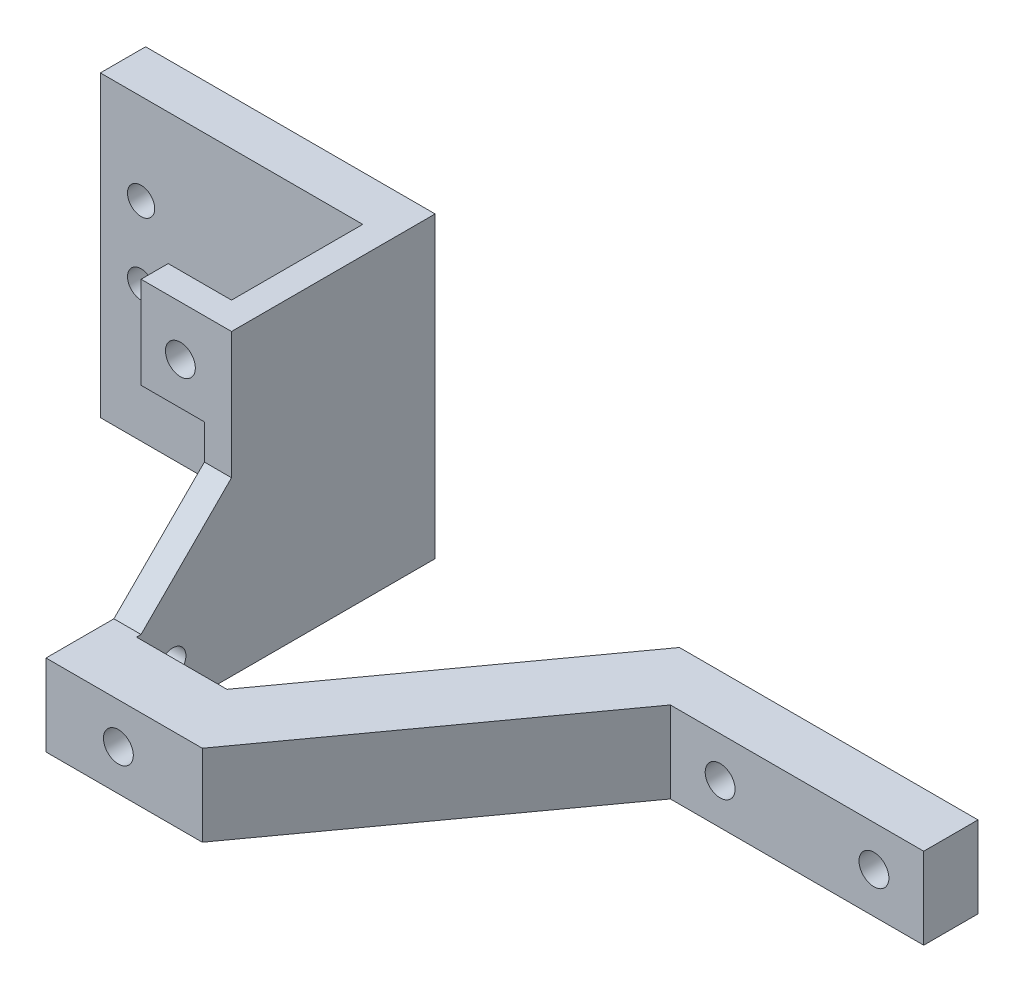
SolidWorks part; units mm, degrees
ref_plane "Płaszczyzna przednia" through (0, 0, 0) normal (0, 0, 1) x (1, 0, 0)
ref_plane "Płaszczyzna górna" through (0, 0, 0) normal (0, 1, 0) x (1, 0, 0)
ref_plane "Płaszczyzna prawa" through (0, 0, 0) normal (1, 0, 0) x (0, 0, -1)
sketch "Szkic1" plane through (0, 0, 0) normal (0, 0, 1) x (1, 0, 0)
  line L0 (0, 0) -> (28, 0)
  line L1 (28, 0) -> (28, 9)
  line L2 (28, 9) -> (0, 9)
  line L3 (0, 9) -> (0, 0)
  line L4 (0, 4.5) -> (28, 4.5) construction
  circle A0 centre (5.5, 4.5) radius 1.65
  circle A1 centre (22.5, 4.5) radius 1.65
  dimension "D3" = 17
  dimension "D1" = 28
  dimension "D2" = 9
  dimension "D4" = 5.5
extrude "Dodanie-wyciągnięcie1" add sketch "Szkic1" along normal blind 6
sketch "Szkic2" plane through (0, 0, 0) normal (0, -1, 0) x (1, 0, 0)
  line L0 (0, 0) -> (-5, 0)
  line L1 (-5, 0) -> (-26, 29.009)
  line L2 (-26, 29.009) -> (-36, 29.009)
  line L3 (-36, 29.009) -> (-36, 36.009)
  line L4 (-36, 36.009) -> (-21.7239, 36.009)
  line L5 (-21.7239, 36.009) -> (0, 6)
  line L6 (0, 6) -> (0, 0)
  dimension "D1" = 21
  dimension "D2" = 7
  dimension "D3" = 5
  dimension "D4" = 10
  dimension "D5" = 14.2761
extrude "Dodanie-wyciągnięcie2" add sketch "Szkic2" against normal up to surface (9 mm away) up to face at (14, 9, 3)
sketch "Szkic3" plane through (0, 0, 0) normal (0, -1, 0) x (1, 0, 0)
  line L0 (-5, 0) -> (28, 0) construction
  line L1 (-36, 36.009) -> (-39, 36.009)
  line L2 (-36, 36.009) -> (-36, -4)
  line L3 (-36, -4) -> (-39, -4)
  line L4 (-39, 36.009) -> (-39, -4)
  dimension "D1" = 3
  dimension "D2" = 4
extrude "Dodanie-wyciągnięcie3" add sketch "Szkic3" against normal up to surface (9 mm away) up to face at (-8.5905, 9, 17.7545)
sketch "Szkic10" plane through (0, 0, 36.009) normal (0, 0, 1) x (1, 0, 0)
  line L0 (-39, 4.5) -> (-21.7239, 4.5) construction
  line L1 (-39, 9) -> (-39, 0) construction
  line L2 (-21.7239, 9) -> (-21.7239, 0) construction
  circle A0 centre (-31, 4.5) radius 1.65
  dimension "D1" = 8
extrude "Wytnij-wyciągnięcie4" cut sketch "Szkic10" against normal up to surface (7 mm away) up to face at (-31, 4.5, 29.009)
sketch "Szkic11" plane through (0, 0, -4) normal (0, 0, -1) x (-1, 0, 0)
  line L0 (36, 9) -> (36, 0) construction
  line L1 (39, 0) -> (36, 0) construction
  line L3 (36, 0) -> (68, 0)
  line L4 (36, 0) -> (36, 33)
  line L5 (36, 33) -> (68, 33)
  line L6 (68, 0) -> (68, 33)
  circle A0 centre (63.5, 15) radius 1.5
  dimension "D2" = 3
  dimension "D1" = 26
  dimension "D3" = 15
  dimension "D4" = 33
  dimension "D5" = 32
extrude "Dodanie-wyciągnięcie4" add sketch "Szkic11" against normal blind 5
sketch "Szkic12" plane through (0, 9, 0) normal (0, 1, 0) x (1, 0, 0)
  line L0 (-39, -1) -> (-39, -36.009) construction
  line L1 (-36, -1) -> (-39, -1)
  line L2 (-36, -1) -> (-36, -18.5045)
  line L3 (-36, -18.5045) -> (-39, -18.5045)
  line L4 (-39, -1) -> (-39, -18.5045)
  line L5 (-68, 4) -> (-36, 4) construction
  dimension "D1" = 22.5045
extrude "Dodanie-wyciągnięcie5" add sketch "Szkic12" along normal up to surface (24 mm away) up to face at (-52, 33, -1.5)
sketch "Szkic13" plane through (0, 33, 0) normal (0, 1, 0) x (1, 0, 0)
  line L1 (-36, -18.5045) -> (-46, -18.5045)
  line L2 (-36, -18.5045) -> (-36, -15.5045)
  line L3 (-36, -15.5045) -> (-46, -15.5045)
  line L4 (-46, -18.5045) -> (-46, -15.5045)
  dimension "D1" = 10
  dimension "D2" = 3
extrude "Dodanie-wyciągnięcie6" add sketch "Szkic13" against normal up to surface (33 mm away) contours L3 L4 L1 L2 up to face at (-23.5603, 0, 11.3363)
sketch "Szkic14" plane through (0, 0, 18.5045) normal (0, 0, 1) x (1, 0, 0)
  line L0 (-46, 33) -> (-36, 33) construction
  line L2 (-36, 33) -> (-36, 9) construction
  circle A0 centre (-41.65, 27.5) radius 1.65
  dimension "D1" = 3.3
  dimension "D2" = 5.5
  dimension "D3" = 4
extrude "Wytnij-wyciągnięcie5" cut sketch "Szkic14" against normal up to surface (3 mm away) up to face at (-42.5, 16.5, 15.5045)
sketch "Szkic15" plane through (0, 0, 18.5045) normal (0, 0, 1) x (1, 0, 0)
  line L1 (-46, 0) -> (-39, 0)
  line L2 (-46, 0) -> (-46, 22.85)
  line L3 (-46, 22.85) -> (-39, 22.85)
  line L4 (-39, 0) -> (-39, 22.85)
  circle A0 centre (-41.65, 27.5) radius 1.65 construction
  dimension "D1" = 3
extrude "Wytnij-wyciągnięcie6" cut sketch "Szkic15" against normal up to surface (3 mm away) up to face at (-43.3, 27.5, 15.5045)
chamfer "Sfazowanie1" distance 10 angle 45 1 edges at (-37.5, 9, 18.5045)
sketch "Szkic16" plane through (0, 0, 1) normal (0, 0, 1) x (1, 0, 0)
  line L0 (-63.5, 15) -> (-63.5, 26.8751) construction
  circle A0 centre (-63.5, 23) radius 1.5
  dimension "D1" = 3
  dimension "D2" = 8
extrude "Wytnij-wyciągnięcie7" cut sketch "Szkic16" against normal up to surface (5 mm away) contours A0 up to face at (-52, 16.5, -4)
sketch "Szkic17" plane through (-39, 0, 0) normal (-1, 0, 0) x (0, 0, 1)
  line L0 (36.009, 0) -> (1, 0) construction
  line L1 (29.009, 9) -> (29.009, 0) construction
  circle A0 centre (25.009, 4.5) radius 1.4629
  dimension "D1" = 4.5
  dimension "D2" = 4
extrude "Wytnij-wyciągnięcie8" cut sketch "Szkic17" against normal up to surface (3 mm away) up to face at (-36, 14.7143, 16.5045)
